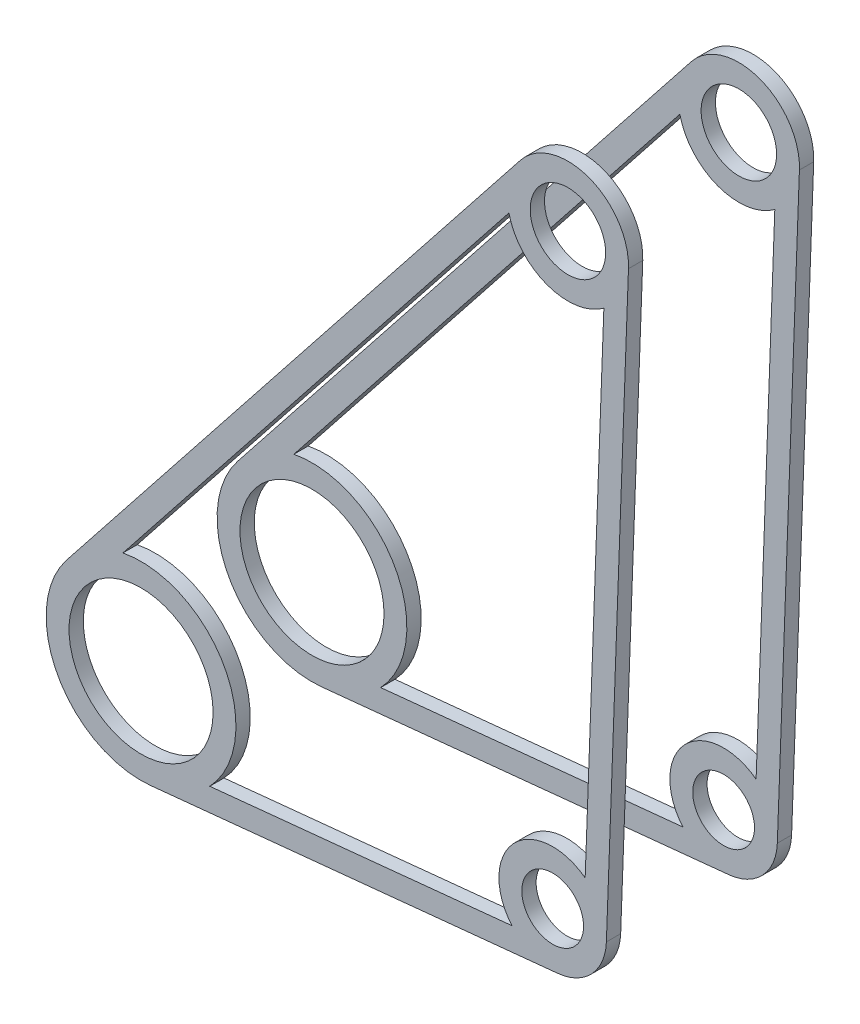
SolidWorks part; units mm, degrees
ref_plane "Front Plane" through (0, 0, 0) normal (0, 0, 1) x (1, 0, 0)
ref_plane "Top Plane" through (0, 0, 0) normal (0, 1, 0) x (1, 0, 0)
ref_plane "Right Plane" through (0, 0, 0) normal (1, 0, 0) x (0, 0, -1)
sketch "Sketch1" plane through (0, 0, 0) normal (0, 0, 1) x (1, 0, 0)
  line L0 (0, 0) -> (45.72, 0) construction
  line L1 (45.72, 0) -> (47.4133, 66.0183) construction
  line L2 (47.4133, 66.0183) -> (0, 0) construction
  line L3 (-8.2641, 6.5435) -> (42.1363, 70.1967)
  line L4 (54.1397, 65.7681) -> (51.6849, -0.2219)
  line L5 (46.3169, -5.9391) -> (1.0541, -10.4882)
  line L6 (-6.2728, 4.9667) -> (44.1276, 68.6199)
  line L7 (0.8001, -7.9609) -> (46.0629, -3.4118)
  line L8 (49.1466, -0.1275) -> (51.6014, 65.8625)
  circle A0 centre (0, 0) radius 8.001
  circle A1 centre (45.72, 0) radius 3.429
  circle A2 centre (47.4133, 66.0183) radius 4.191
  circle A3 centre (0, 0) radius 10.541
  circle A4 centre (45.72, 0) radius 5.969
  circle A5 centre (47.4133, 66.0183) radius 6.731
  dimension "D1" = 8.382
  dimension "D2" = 6.858
  dimension "D3" = 16.002
  dimension "D6" = 2.54
  dimension "D7" = 2.54
  dimension "D8" = 2.54
  dimension "D5" = 66.04
  dimension "2.7" = 45.72
  dimension "D9" = 81.28
extrude "Boss-Extrude1" add sketch "Sketch1" along normal blind 1.5875 from offset 8.6995 contours A5 L3 A3 L6 | L6 A3 A0 | A4 A3 L5 | A4 L8 A1 | A5 L8 A4 L4 | A5 L6 A2 L8 | A3 L6 A0 | L8 A4 A1 | L6 A5 L8 A2 region at (-5.3351, 8.7687, 0) region at (18.2248, 37.9962, 0) region at (49.5658, 72.2042, 0) region at (24.179, -6.9398, 0) region at (6.5454, 7.9412, 0) region at (42.6044, 66.4669, 0) region at (43.5656, -5.4055, 0) region at (51.6669, 32.6998, 0) region at (41.4687, 3.9916, 0)
extrude "Boss-Extrude2" add sketch "Sketch1<4>" against normal blind 1.5875 from offset 8.6995 separate body contours A5 L3 A3 L6 | L6 A3 A0 | A3 L6 A0 | A4 A3 L5 | A4 L8 A1 | L8 A4 A1 | A5 L8 A4 L4 | L6 A5 L8 A2 | A5 L6 A2 L8 region at (-5.3351, 8.7687, 0) region at (18.2248, 37.9962, 0) region at (49.5658, 72.2042, 0) region at (24.179, -6.9398, 0) region at (6.5454, 7.9412, 0) region at (42.6044, 66.4669, 0) region at (43.5656, -5.4055, 0) region at (51.6669, 32.6998, 0) region at (41.4687, 3.9916, 0) offset against normal yes
sketch "Sketch1<4>" plane through (0, 0, 0) normal (0, 0, 1) x (1, 0, 0) same geometry as "Sketch1"
equation "\"D19@Boss-Extrude2\"=.45"
